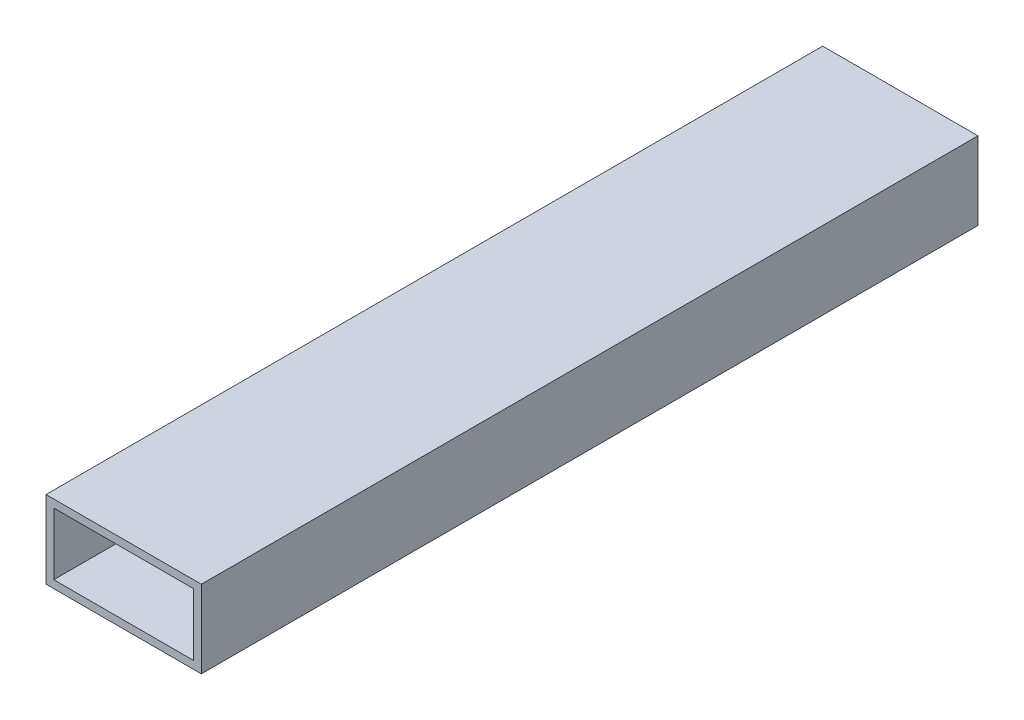
SolidWorks part; units mm, degrees
material "6061 Alloy"
ref_plane "Front Plane" through (0, 0, 0) normal (0, 0, 1) x (1, 0, 0)
ref_plane "Top Plane" through (0, 0, 0) normal (0, 1, 0) x (1, 0, 0)
ref_plane "Right Plane" through (0, 0, 0) normal (1, 0, 0) x (0, 0, -1)
sketch "Sketch1" plane through (0, 0, 0) normal (0, 0, 1) x (1, 0, 0)
  line L1 (-12.7, 6.35) -> (12.7, 6.35)
  line L2 (-12.7, 6.35) -> (-12.7, -6.35)
  line L3 (-12.7, -6.35) -> (12.7, -6.35)
  line L4 (12.7, 6.35) -> (12.7, -6.35)
  point P4 (-12.7, 0)
  point P6 (0, 6.35)
  dimension "D1" = 12.7
  dimension "D2" = 25.4
extrude "Boss-Extrude1" add sketch "Sketch1" along normal blind 127
sketch "Sketch4" plane through (0, 0, 0) normal (0, 0, -1) x (-1, 0, 0)
  line L0 (-12.7, -6.35) -> (-12.7, 6.35) construction
  line L1 (-11.43, 5.08) -> (11.43, 5.08)
  line L2 (-11.43, 5.08) -> (-11.43, -5.08)
  line L3 (-11.43, -5.08) -> (11.43, -5.08)
  line L4 (11.43, 5.08) -> (11.43, -5.08)
  line L5 (-12.7, 6.35) -> (12.7, 6.35) construction
  line L6 (12.7, -6.35) -> (-12.7, -6.35) construction
  line L7 (12.7, 6.35) -> (12.7, -6.35) construction
  dimension "D1" = 1.27
  dimension "D2" = 1.27
  dimension "D3" = 1.27
  dimension "D4" = 1.27
extrude "Cut-Extrude1" cut sketch "Sketch4" against normal through all
